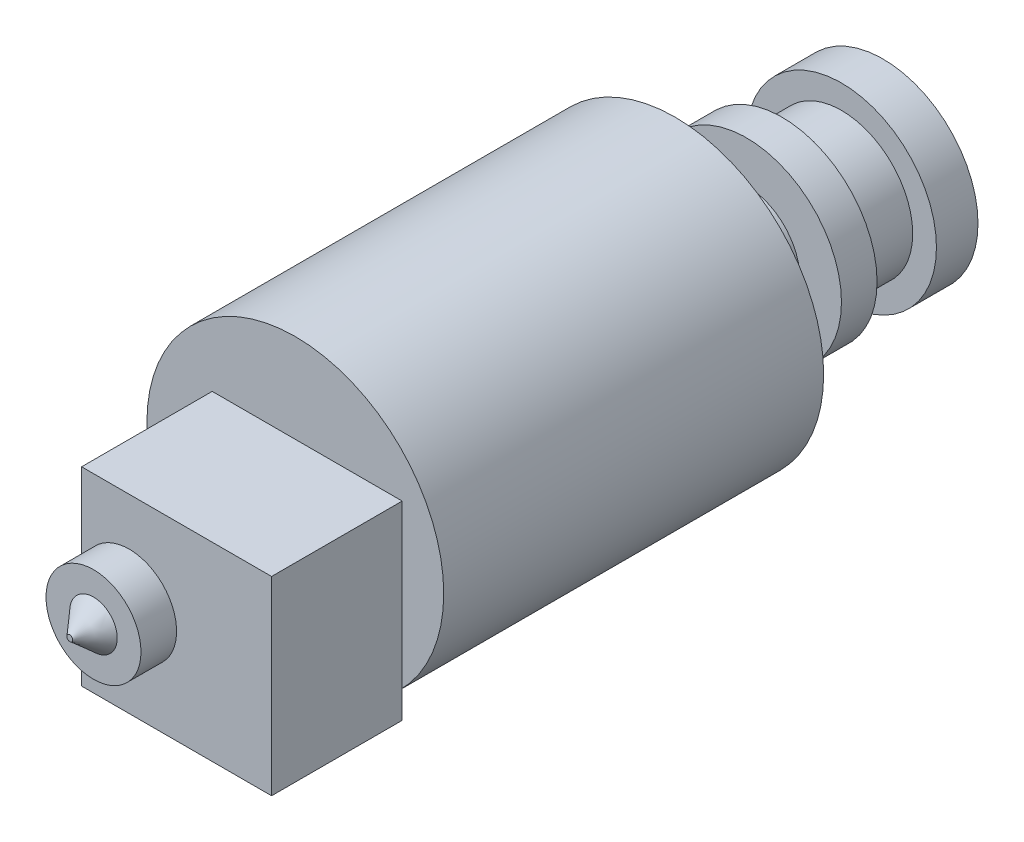
SolidWorks part; units mm, degrees
ref_plane "Front Plane" through (0, 0, 0) normal (0, 0, 1) x (1, 0, 0)
ref_plane "Top Plane" through (0, 0, 0) normal (0, 1, 0) x (1, 0, 0)
ref_plane "Right Plane" through (0, 0, 0) normal (1, 0, 0) x (0, 0, -1)
sketch "Sketch1" plane through (0, 0, 0) normal (0, 0, 1) x (1, 0, 0)
  circle A0 centre (0, 0) radius 8
  dimension "D1" = 16
extrude "Boss-Extrude1" add sketch "Sketch1" along normal blind 3.5
sketch "Sketch2" plane through (0, 0, 3.5) normal (0, 0, 1) x (1, 0, 0)
  circle A0 centre (0, 0) radius 6
  dimension "D1" = 12
extrude "Boss-Extrude2" add sketch "Sketch2" along normal blind 5
sketch "Sketch3" plane through (0, 0, 8.5) normal (0, 0, 1) x (1, 0, 0)
  circle A0 centre (0, 0) radius 8
  dimension "D1" = 16
extrude "Boss-Extrude3" add sketch "Sketch3" along normal blind 3
sketch "Sketch4" plane through (0, 0, 11.5) normal (0, 0, 1) x (1, 0, 0)
  circle A0 centre (0, 0) radius 4.5
  dimension "D1" = 9
extrude "Boss-Extrude4" add sketch "Sketch4" along normal blind 6
sketch "Sketch5" plane through (0, 0, 17.5) normal (0, 0, 1) x (1, 0, 0)
  circle A0 centre (0, 0) radius 12.5
  dimension "D1" = 25
extrude "Boss-Extrude5" add sketch "Sketch5" along normal blind 32
sketch "Sketch6" plane through (0, 0, 49.5) normal (0, 0, 1) x (1, 0, 0)
  circle A0 centre (0, 0) radius 3
  dimension "D1" = 6
extrude "Boss-Extrude6" add sketch "Sketch6" along normal blind 3
sketch "Sketch7" plane through (0, 0, 52.5) normal (0, 0, 1) x (1, 0, 0)
  line L1 (-4, -8) -> (12, -8)
  line L2 (-4, -8) -> (-4, 8)
  line L3 (-4, 8) -> (12, 8)
  line L4 (12, -8) -> (12, 8)
  line L5 (-4, -8) -> (12, 8) construction
  line L6 (-4, 8) -> (12, -8) construction
  circle A0 centre (0, 0) radius 3 construction
  point P0 (4, 0)
  dimension "D3" = 12
  dimension "D1" = 16
  dimension "D2" = 16
extrude "Boss-Extrude7" add sketch "Sketch7" along normal blind 11
sketch "Sketch8" plane through (0, 0, 63.5) normal (0, 0, 1) x (1, 0, 0)
  circle A0 centre (0, 0) radius 4
  dimension "D1" = 8
extrude "Boss-Extrude8" add sketch "Sketch8" along normal blind 3
sketch "Sketch9" plane through (0, 0, 66.5) normal (0, 0, 1) x (1, 0, 0)
  circle A0 centre (0, 0) radius 2
  dimension "D1" = 4
sketch "Sketch10" plane through (0, 0, 0) normal (0, 0, -1) x (-1, 0, 0)
  circle A0 centre (0, 0) radius 1.5
  dimension "D1" = 3
extrude "Cut-Extrude1" cut sketch "Sketch10" against normal blind 2
ref_plane "Plane2" through (0, 0, 68.5) normal (0, 0, 1) x (1, 0, 0)
sketch "Sketch12" plane through (0, 0, 68.5) normal (0, 0, 1) x (1, 0, 0)
  circle A0 centre (0, 0) radius 0.25
  dimension "D1" = 0.5
loft "Loft1" add profiles "Sketch12", "Sketch9" connector at (-0.2472, 0.0376, 68.5) connector at (-1.9192, -0.5628, 66.5)
